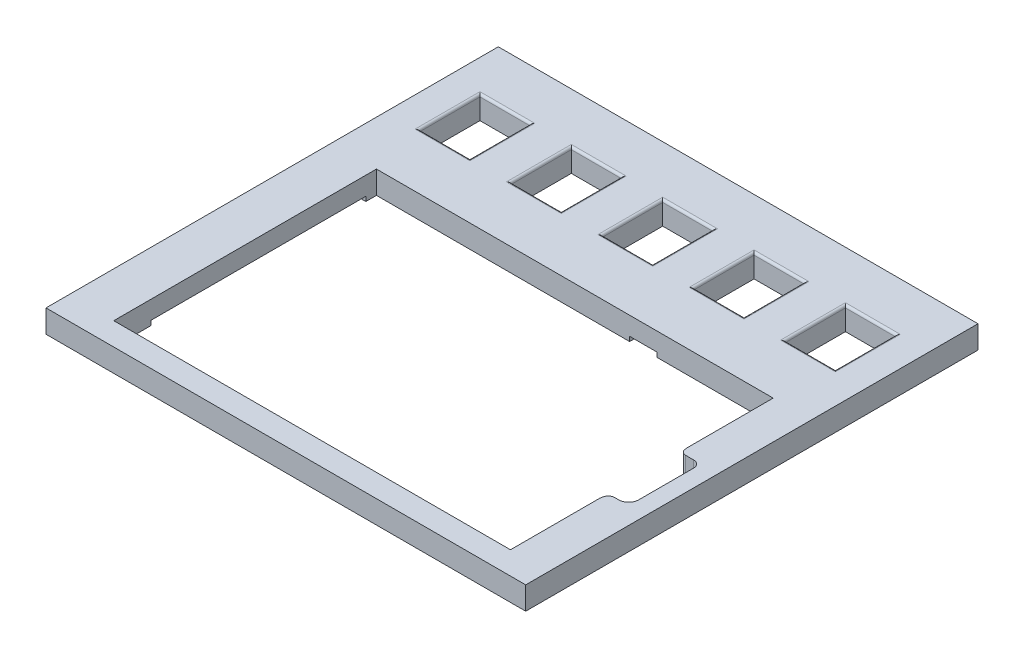
SolidWorks part; units mm, degrees
ref_plane "Front Plane" through (0, 0, 0) normal (0, 0, 1) x (1, 0, 0)
ref_plane "Top Plane" through (0, 0, 0) normal (0, 1, 0) x (1, 0, 0)
ref_plane "Right Plane" through (0, 0, 0) normal (1, 0, 0) x (0, 0, -1)
sketch "Sketch1" plane through (0, 0, 0) normal (0, 1, 0) x (1, 0, 0)
  line L1 (52.5, -34.5) -> (-52.5, -34.5)
  line L2 (52.5, -34.5) -> (52.5, 34.5)
  line L3 (52.5, 34.5) -> (-52.5, 34.5)
  line L4 (-52.5, -34.5) -> (-52.5, 34.5)
  line L5 (52.5, -34.5) -> (-52.5, 34.5) construction
  line L6 (52.5, 34.5) -> (-52.5, -34.5) construction
  point P0 (0, 0)
  dimension "D1" = 105
  dimension "D2" = 69
extrude "Boss-Extrude1" add sketch "Sketch1" along normal blind 5
extrude "Cut-Extrude1" cut sketch "Sketch2" against normal through all
sketch "Sketch2" plane through (17.0721, 0, 5.1034) normal (0, -1, 0) x (-1, 0, 0)
  line L0 (59.7281, 33.0909) -> (-27.1079, 33.0909)
  line L1 (-27.1079, 33.0909) -> (-27.1079, -24.4081)
  line L2 (-27.1079, -24.4081) -> (59.7281, -24.4081)
  line L3 (59.7281, -24.4081) -> (59.7281, 33.0909)
  line L8 (-26.1079, -23.4081) -> (58.7281, -23.4081) construction
  line L9 (-26.1079, 32.0909) -> (-26.1079, -23.4081) construction
  line L10 (58.7281, 32.0909) -> (-26.1079, 32.0909) construction
  line L11 (58.7281, -23.4081) -> (58.7281, 32.0909) construction
extrude "Cut-Extrude2" cut sketch "Sketch3" against normal blind 1
sketch "Sketch3" plane through (17.0721, 0, 5.1034) normal (0, -1, 0) x (-1, 0, 0)
  line L1 (59.8221, 30.7659) -> (54.5248, 30.7659)
  line L2 (59.8221, 30.7659) -> (59.8221, -16.2341) construction
  line L3 (59.8221, -16.2341) -> (54.5248, -16.2341)
  line L8 (65.3221, 30.2659) -> (60.3221, 30.2659) construction
  line L9 (60.3221, 30.2659) -> (60.3221, -15.7341) construction
  line L10 (60.3221, -15.7341) -> (65.3221, -15.7341) construction
  line L11 (65.3221, -15.7341) -> (65.3221, 30.2659) construction
  line L12 (54.5248, 30.7659) -> (54.5248, -16.2341)
  line L20 (65.8221, 30.7659) -> (59.8221, 30.7659)
  line L21 (59.8221, 30.7659) -> (59.8221, -16.2341) construction
  line L22 (59.8221, -16.2341) -> (65.8221, -16.2341)
  line L23 (65.8221, -16.2341) -> (65.8221, 30.7659)
extrude "Cut-Extrude3" cut sketch "Sketch4" against normal blind 1 contours L31 L28 L29 L17 L16 L19 | L19 L16 L17 | L30 L31 L19 L18 L17 L29 | L18 L19 L17 region at (15.76, 0, -28.9025) region at (12.8295, 0, -28.9025)
sketch "Sketch4" plane through (17.0721, 0, 5.1034) normal (0, -1, 0) x (-1, 0, 0)
  line L8 (69.5721, -29.3966) -> (69.5721, 69.6034)
  line L10 (-35.4279, 69.6034) -> (-35.4279, -29.3966)
  line L11 (-35.4279, -29.3966) -> (69.5721, -29.3966)
  line L16 (3.8121, 35.2559) -> (-1.1879, 35.2559)
  line L17 (-1.1879, 35.2559) -> (-1.1879, 32.7559)
  line L18 (-1.1879, 32.7559) -> (3.8121, 32.7559)
  line L19 (3.8121, 32.7559) -> (3.8121, 35.2559)
  line L20 (69.5721, 69.6034) -> (-35.4279, 69.6034)
  line L28 (4.3121, 35.7559) -> (-1.6879, 35.7559)
  line L29 (-1.6879, 35.7559) -> (-1.6879, 32.2559)
  line L30 (-1.6879, 32.2559) -> (4.3121, 32.2559)
  line L31 (4.3121, 32.2559) -> (4.3121, 35.7559)
extrude "Cut-Extrude4" cut sketch "Sketch5" against normal through all contours L3 L2 A3 L5 A2 L4 | L2 L3 L4 A4 L6 A5 region at (42.0883, 0, 0.4104)
sketch "Sketch5" plane through (17.0721, 0, 5.1034) normal (0, -1, 0) x (-1, 0, 0)
  line L2 (-27.1779, 33.1034) -> (-27.1779, 13.8376)
  line L3 (-27.1779, 5.1034) -> (-31.6779, 5.1034) construction
  line L4 (-31.6779, -0.8966) -> (-31.6779, 11.1034)
  line L5 (-30.1159, 12.6653) -> (-28.3501, 12.6653)
  line L6 (-29.4785, -3.0961) -> (-28.6478, -3.0961)
  line L7 (-27.1779, 5.1034) -> (-27.1779, 13.8376) construction
  line L8 (-27.1779, -4.566) -> (-18.8659, -4.566)
  line L9 (-27.1779, -4.566) -> (-27.1779, 5.1034)
  line L10 (-27.1779, 13.8376) -> (-18.8659, 13.8376)
  line L11 (-18.8659, -4.566) -> (-18.8659, 13.8376)
  line L12 (-27.1779, 13.8376) -> (-27.1779, 5.1034) construction
  line L13 (-27.1779, 5.1034) -> (-27.1779, -22.8966)
  arc A2 (-31.6779, 11.1034) -> (-30.1159, 12.6653) centre (-30.1159, 11.1034) cw
  arc A3 (-28.3501, 12.6653) -> (-27.1779, 13.8376) centre (-28.3501, 13.8376) ccw
  arc A4 (-31.6779, -0.8966) -> (-29.4785, -3.0961) centre (-29.4785, -0.8966) ccw
  arc A5 (-28.6478, -3.0961) -> (-27.1779, -4.566) centre (-28.6478, -4.566) cw
  point P8 (-31.6779, 5.1034)
extrude "Cut-Extrude7" cut sketch "Sketch9" against normal blind 3
sketch "Sketch9" plane through (17.0721, 0, 5.1034) normal (0, -1, 0) x (-1, 0, 0)
  circle A4 centre (-28.6779, -22.8966) radius 1.5 construction
  circle A5 centre (62.8221, -22.8966) radius 1.5 construction
  circle A6 centre (62.8221, 33.1034) radius 1.5 construction
  circle A7 centre (-28.6779, 33.1034) radius 1.5 construction
  circle A8 centre (-28.6779, 33.1034) radius 1
  circle A9 centre (62.8221, 33.1034) radius 1
  circle A10 centre (-28.6779, -22.8966) radius 1
  circle A11 centre (62.8221, -22.8966) radius 1
sketch "Sketch7" plane through (0, 5, 0) normal (0, 1, 0) x (1, 0, 0)
  line L1 (52.5, 34.5) -> (-52.5, 34.5)
  line L2 (52.5, 34.5) -> (52.5, 64.5)
  line L3 (52.5, 64.5) -> (-52.5, 64.5)
  line L4 (-52.5, 34.5) -> (-52.5, 64.5)
  dimension "D1" = 30
extrude "Boss-Extrude2" add sketch "Sketch7" against normal up to surface (5 mm away) up to face at (-45.75, 0, -29)
sketch "Sketch8" plane through (0, 5, 0) normal (0, 1, 0) x (1, 0, 0)
  line L0 (52.5, 29.2726) -> (52.5, 64.5) construction
  line L1 (52.5, -34.5) -> (52.5, 64.5) construction
  line L2 (52.5, 46.8863) -> (-52.5, 46.8863) construction
  line L3 (-52.5, 64.5) -> (-52.5, -34.5) construction
  line L4 (25.5, 40.2863) -> (25.5, 53.4863)
  line L5 (45.5, 40.2863) -> (34.5, 40.2863)
  line L6 (45.5, 40.2863) -> (45.5, 53.4863)
  line L7 (45.5, 53.4863) -> (34.5, 53.4863)
  line L8 (34.5, 40.2863) -> (34.5, 53.4863)
  line L9 (45.5, 40.2863) -> (34.5, 53.4863) construction
  line L10 (45.5, 53.4863) -> (34.5, 40.2863) construction
  line L11 (25.5, 40.2863) -> (14.5, 40.2863)
  line L12 (14.5, 40.2863) -> (14.5, 53.4863)
  line L13 (25.5, 53.4863) -> (14.5, 53.4863)
  line L14 (5.5, 40.2863) -> (5.5, 53.4863)
  line L15 (5.5, 40.2863) -> (-5.5, 40.2863)
  line L16 (-5.5, 40.2863) -> (-5.5, 53.4863)
  line L17 (5.5, 53.4863) -> (-5.5, 53.4863)
  line L18 (-14.5, 40.2863) -> (-14.5, 53.4863)
  line L19 (-14.5, 40.2863) -> (-25.5, 40.2863)
  line L20 (-25.5, 40.2863) -> (-25.5, 53.4863)
  line L21 (-14.5, 53.4863) -> (-25.5, 53.4863)
  line L22 (-34.5, 40.2863) -> (-34.5, 53.4863)
  line L23 (-34.5, 40.2863) -> (-45.5, 40.2863)
  line L24 (-45.5, 40.2863) -> (-45.5, 53.4863)
  line L25 (-34.5, 53.4863) -> (-45.5, 53.4863)
  point P9 (40, 46.8863)
  point P14 (-40, 53.4863)
  dimension "D1" = 13.2
  dimension "D2" = 11
  dimension "D3" = 12.5
  dimension "D5" = 12.5
  dimension "D6" = 11
  dimension "D4" = 5
extrude "Cut-Extrude6" cut sketch "Sketch8" against normal through all
fillet "Fillet1" radius 0.5 20 edges at (-40, 5, -53.4863) (-45.5, 5, -46.8863) (-34.5, 5, -46.8863) (-40, 5, -40.2863) (-20, 5, -53.4863) (-25.5, 5, -46.8863) (-20, 5, -40.2863) (-14.5, 5, -46.8863) (5.5, 5, -46.8863) (0, 5, -40.2863) (-5.5, 5, -46.8863) (0, 5, -53.4863) (20, 5, -53.4863) (40, 5, -53.4863) (14.5, 5, -46.8863) (25.5, 5, -46.8863) (20, 5, -40.2863) (34.5, 5, -46.8863) (45.5, 5, -46.8863) (40, 5, -40.2863)
fillet "Fillet3" radius 1 2 edges at (44.18, 2.5, 9.6693) (44.18, 2.5, -8.7342)
